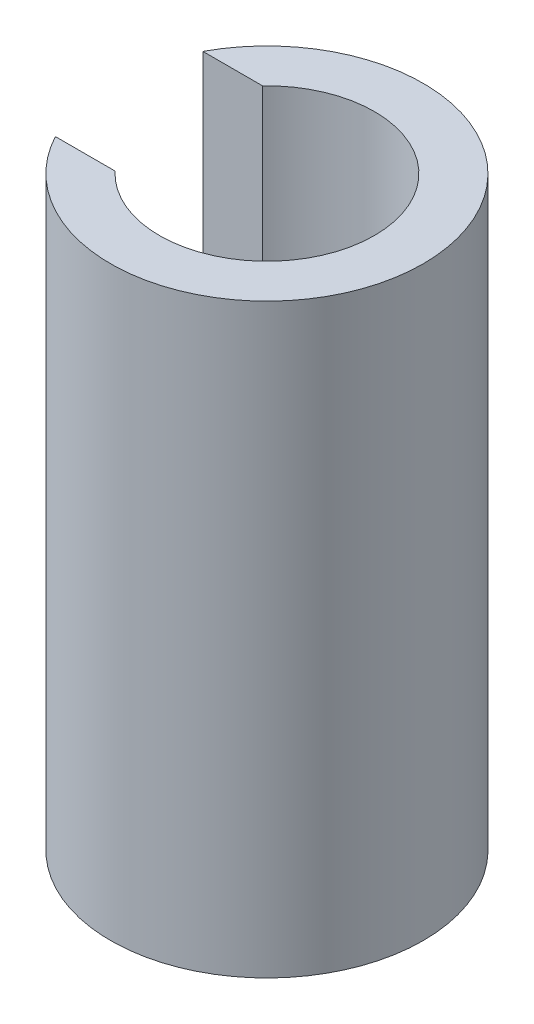
SolidWorks part; units mm, degrees
ref_plane "前基準面" through (0, 0, 0) normal (0, 0, 1) x (1, 0, 0)
ref_plane "上基準面" through (0, 0, 0) normal (0, 1, 0) x (1, 0, 0)
ref_plane "右基準面" through (0, 0, 0) normal (1, 0, 0) x (0, 0, -1)
ref_axis "基準軸1" through (0, -55, 0) along (0, 1, 0)
ref_axis "基準軸2" through (-88.99, 0, 0) along (1, 0, 0)
ref_axis "基準軸3" through (0, 0, 55) along (0, 0, -1)
sketch "草圖1" plane through (0, 0, 0) normal (0, 1, 0) x (1, 0, 0)
  circle A0 centre (0, 0) radius 2.75
  circle A1 centre (0, 0) radius 4
  dimension "D1" = 5.5
  dimension "D2" = 8
extrude "填料-伸長1" add sketch "草圖1" along normal blind 15
sketch "草圖2" plane through (0, 15, 0) normal (0, 1, 0) x (1, 0, 0)
  line L1 (-4, -1.8875) -> (-2, -1.8875)
  line L2 (-4, -1.8875) -> (-4, 1.8875)
  line L3 (-4, 1.8875) -> (-2, 1.8875)
  line L4 (-2, -1.8875) -> (-2, 1.8875)
  line L5 (-55, 0) -> (55, 0) construction
  circle A0 centre (0, 0) radius 4 construction
  circle A1 centre (0, 0) radius 2.75 construction
  point P4 (-2, 0)
  dimension "D1" = 2
extrude "除料-伸長1" cut sketch "草圖2" against normal blind 15
